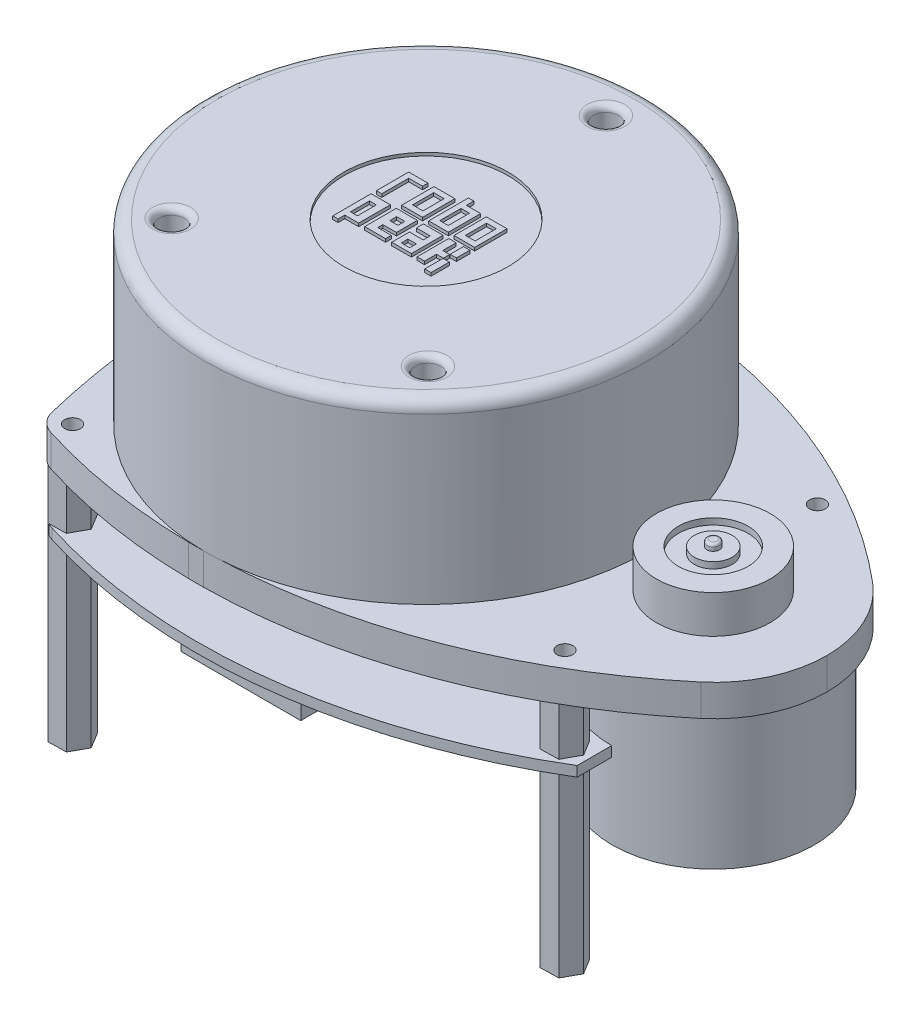
SolidWorks part; units mm, degrees
ref_plane "Спереди" through (0, 0, 0) normal (0, 0, 1) x (1, 0, 0)
ref_plane "Сверху" through (0, 0, 0) normal (0, 1, 0) x (1, 0, 0)
ref_plane "Справа" through (0, 0, 0) normal (1, 0, 0) x (0, 0, -1)
sketch "Эскиз1" plane through (0, 0, 0) normal (0, 1, 0) x (1, 0, 0)
  line L1 (-49.25, 35) -> (49.25, 35)
  line L2 (-49.25, 35) -> (-49.25, -35)
  line L3 (-49.25, -35) -> (49.25, -35)
  line L4 (49.25, 35) -> (49.25, -35)
  line L5 (-49.25, 35) -> (49.25, -35) construction
  line L6 (-49.25, -35) -> (49.25, 35) construction
  point P0 (0, 0)
  dimension "D1" = 98.5
  dimension "D2" = 70
extrude "Бобышка-Вытянуть1" add sketch "Эскиз1" along normal blind 5
sketch "Эскиз2" plane through (0, 5, 0) normal (0, 1, 0) x (1, 0, 0)
  line L0 (-49.25, 35) -> (-49.25, -35) construction
  circle A0 centre (-14.25, 0) radius 35
  point P2 (-49.25, 0)
  point P3 (-49.25, 0)
extrude "Бобышка-Вытянуть2" add sketch "Эскиз2" along normal blind 28.1
sketch "Эскиз3" plane through (0, 33.1, 0) normal (0, 1, 0) x (1, 0, 0)
  line L0 (-14.25, 0) -> (-14.25, 50000) construction
  line L1 (-14.25, -20) -> (-26.2883, -20) construction
  line L2 (-49.25, -35) -> (-14.25, -35) construction
  circle A0 centre (-14.25, 28.5) radius 2
  circle A1 centre (-34.5539, -20) radius 2
  circle A2 centre (6.0539, -20) radius 2
  arc A3 (-49.25, 0) -> (-14.25, -35) centre (-14.25, 0) ccw construction
  circle A4 centre (-14.25, 0) radius 35 construction
  dimension "D2" = 4
  dimension "D1" = 6.5
  dimension "D3" = 15
  dimension "D4" = 28.5
  dimension "D5" = 28.5
extrude "Вырез-Вытянуть1" cut sketch "Эскиз3" against normal blind 5
fillet "Скругление1" radius 2 1 edges at (-14.25, 33.1, 35)
fillet "Скругление2" radius 1 3 edges at (6.0539, 33.1, 22) (-34.5539, 33.1, 22) (-14.25, 33.1, -26.5)
sketch "Эскиз4" plane through (0, 33.1, 0) normal (0, 1, 0) x (1, 0, 0)
  line L0 (-22.1152, -6.9149) -> (-22.1152, -0.8316)
  line L1 (-22.1152, -0.8316) -> (-19.0735, -0.8316)
  line L2 (-19.0735, -0.8316) -> (-19.0735, -5.8538)
  line L3 (-19.0735, -5.8538) -> (-21.2663, -5.8538)
  line L4 (-21.2663, -5.8538) -> (-21.2663, -6.9149)
  line L5 (-21.2663, -6.9149) -> (-22.1152, -6.9149)
  line L6 (-22.1152, 0) -> (-22.1152, 5.1201)
  line L7 (-22.1152, 5.1201) -> (-19.0735, 5.1201)
  line L8 (-19.0735, 5.1201) -> (-19.0735, 4.2707)
  line L9 (-19.0735, 4.2707) -> (-21.2663, 4.2707)
  line L10 (-21.2663, 4.2707) -> (-21.2663, 0)
  line L11 (-21.2663, 0) -> (-22.1152, 0)
  line L12 (-21.2663, -1.9579) -> (-20.1699, -1.9579)
  line L13 (-20.1699, -1.9579) -> (-20.1699, -4.9509)
  line L14 (-20.1699, -4.9509) -> (-21.2663, -4.9509)
  line L15 (-21.2663, -4.9509) -> (-21.2663, -1.9579)
  line L16 (-13.8296, 0) -> (-13.8296, 6.293)
  line L17 (-18.1168, 0) -> (-14.8003, 0)
  line L18 (-18.1168, 0) -> (-18.1168, 5.1201)
  line L19 (-18.1168, 5.1201) -> (-14.8003, 5.1201)
  line L20 (-14.8003, 0) -> (-14.8003, 5.1201)
  line L21 (-9.8255, 5.1201) -> (-6.5494, 5.1201)
  line L22 (-9.8255, 5.1201) -> (-9.8255, 0)
  line L23 (-9.8255, 0) -> (-6.5494, 0)
  line L24 (-6.5494, 5.1201) -> (-6.5494, 0)
  line L25 (-8.9357, 4.2707) -> (-7.3988, 4.2707)
  line L26 (-8.9357, 4.2707) -> (-8.9357, 0.9137)
  line L27 (-8.9357, 0.9137) -> (-7.3988, 0.9137)
  line L28 (-7.3988, 4.2707) -> (-7.3988, 0.9137)
  line L29 (-17.3079, 4.2707) -> (-15.6497, 4.2707)
  line L30 (-17.3079, 4.2707) -> (-17.3079, 0.9137)
  line L31 (-17.3079, 0.9137) -> (-15.6497, 0.9137)
  line L32 (-15.6497, 4.2707) -> (-15.6497, 0.9137)
  line L33 (-12.9802, 4.2707) -> (-11.6455, 4.2707)
  line L34 (-12.9802, 4.2707) -> (-12.9802, 0.9137)
  line L35 (-12.9802, 0.9137) -> (-11.6455, 0.9137)
  line L36 (-11.6455, 4.2707) -> (-11.6455, 0.9137)
  line L37 (-12.9802, -4.142) -> (-11.6455, -4.142)
  line L38 (-12.9802, -4.142) -> (-12.9802, -5.1936)
  line L39 (-12.9802, -5.1936) -> (-11.6455, -5.1936)
  line L40 (-11.6455, -4.142) -> (-11.6455, -5.1936)
  line L41 (-16.9439, -1.9579) -> (-15.6497, -1.9579)
  line L42 (-16.9439, -1.9579) -> (-16.9439, -3.0499)
  line L43 (-16.9439, -3.0499) -> (-15.6497, -3.0499)
  line L44 (-15.6497, -1.9579) -> (-15.6497, -3.0499)
  line L46 (-7.5508, -0.7643) -> (-6.5494, -0.7643)
  line L47 (-7.5508, -0.7643) -> (-7.5508, -2.8858)
  line L48 (-7.5508, -2.8858) -> (-6.5494, -2.8858)
  line L49 (-6.5494, -0.7643) -> (-6.5494, -2.8858)
  line L50 (-6.5494, -6.9149) -> (-7.5508, -6.9149)
  line L51 (-6.5494, -6.9149) -> (-6.5494, -4.0216)
  line L52 (-6.5494, -4.0216) -> (-7.5508, -4.0216)
  line L53 (-13.8296, 6.293) -> (-12.9802, 6.293)
  line L54 (-12.9802, 6.293) -> (-12.9802, 5.1201)
  line L55 (-12.9802, 5.1201) -> (-10.7153, 5.1201)
  line L56 (-10.7153, 5.1201) -> (-10.7153, 0)
  line L57 (-10.7153, 0) -> (-13.8296, 0)
  line L58 (-9.8255, -0.8316) -> (-8.6437, -0.8316)
  line L59 (-8.6437, -0.8316) -> (-8.6437, -2.9608)
  line L60 (-8.6437, -2.9608) -> (-7.5508, -2.9608)
  line L61 (-9.8255, -0.8316) -> (-9.8255, -5.8538)
  line L62 (-9.8255, -5.8538) -> (-8.6437, -5.8538)
  line L63 (-8.6437, -5.8538) -> (-8.6437, -3.9573)
  line L64 (-8.6437, -3.9573) -> (-7.5508, -3.9573)
  line L65 (-7.5508, -2.9608) -> (-7.5508, -3.9573)
  line L66 (-13.8296, -0.8316) -> (-10.7153, -0.8316)
  line L67 (-10.7153, -0.8316) -> (-10.7153, -5.8538)
  line L68 (-10.7153, -5.8538) -> (-13.8296, -5.8538)
  line L69 (-13.8296, -5.8538) -> (-13.8296, -3.0499)
  line L70 (-13.8296, -3.0499) -> (-11.6455, -3.0499)
  line L71 (-11.6455, -3.0499) -> (-11.6455, -1.9408)
  line L72 (-11.6455, -1.9408) -> (-13.8296, -1.9408)
  line L73 (-13.8296, -1.9408) -> (-13.8296, -0.8316)
  line L74 (-18.1168, -0.8316) -> (-14.8003, -0.8316)
  line L75 (-14.8003, -0.8316) -> (-14.8003, -4.142)
  line L76 (-14.8003, -4.142) -> (-16.9439, -4.142)
  line L77 (-16.9439, -4.142) -> (-16.9439, -4.9509)
  line L78 (-16.9439, -4.9509) -> (-14.8003, -4.9509)
  line L79 (-14.8003, -4.9509) -> (-14.8003, -5.8538)
  line L80 (-14.8003, -5.8538) -> (-18.1168, -5.8538)
  line L81 (-18.1168, -5.8538) -> (-18.1168, -0.8316)
  line L82 (-7.5508, -6.9149) -> (-7.5508, -4.0216)
  circle A0 centre (-14.25, 0) radius 13
  dimension "D1" = 26
extrude "Вырез-Вытянуть3" cut sketch "Эскиз4" against normal blind 0.5 contours A0 L50 L82 L52 L51 L72 L73 L66 L67 L68 L69 L70 L71 L56 L57 L16 L53 L54 L55 L10 L11 L6 L7 L8 L9 L4 L5 L0 L1 L2 L3 L20 L17 L18 L19 L21 L24 L23 L22 L46 L49 L48 L47 | L32 L29 L30 L31 | L36 L33 L34 L35 | L28 L25 L26 L27 | L44 L41 L42 L43 | L15 L14 L13 L12 | L37 L40 L39 L38 region at (-20.7181, 33.1, 3.4544) region at (-8.1672, 33.1, -2.5922) region at (-16.4788, 33.1, -2.5922) region at (-12.3129, 33.1, -2.5922) region at (-16.2968, 33.1, 2.5039) region at (-14.2871, 33.1, -0.0991)
sketch "Эскиз5" plane through (0, 5, 0) normal (0, 1, 0) x (1, 0, 0)
  line L0 (-42.25, 30.7255) -> (-42.25, -39.5827) construction
  line L1 (27.75, 26.9972) -> (27.75, -49973.0028) construction
  line L2 (-49.25, 0) -> (49950.75, 0) construction
  circle A0 centre (-14.25, 0) radius 33 construction
  circle A1 centre (-42.25, 28) radius 1.25
  circle A2 centre (27.75, 20) radius 1.25
  circle A3 centre (27.75, -20) radius 1.25
  circle A4 centre (-42.25, -28) radius 1.25
  point P4 (-14.25, 33)
  dimension "D1" = 28
  dimension "D3" = 2.5
  dimension "D2" = 42
  dimension "D4" = 28
  dimension "D5" = 20
extrude "Вырез-Вытянуть4" cut sketch "Эскиз5" against normal blind 5
sketch "Эскиз6" plane through (0, 5, 0) normal (0, 1, 0) x (1, 0, 0)
  line L0 (49.25, 0) -> (50049.25, 0) construction
  line L1 (49.25, -35) -> (49.25, 35) construction
  circle A0 centre (31.25, 0) radius 9
  arc A1 (-14.25, -35) -> (-14.25, 35) centre (-14.25, 0) ccw construction
  point P4 (49.25, 0)
  dimension "D1" = 18
  dimension "D2" = 45.5
extrude "Бобышка-Вытянуть3" add sketch "Эскиз6" along normal blind 7
sketch "Эскиз7" plane through (0, 12, 0) normal (0, 1, 0) x (1, 0, 0)
  circle A0 centre (31.25, 0) radius 9
  circle A1 centre (31.25, 0) radius 0.9935
extrude "Вырез-Вытянуть5" cut sketch "Эскиз7" against normal blind 1
sketch "Эскиз8" plane through (0, 11, 0) normal (0, 1, 0) x (1, 0, 0)
  circle A0 centre (31.25, 0) radius 3.0011
  circle A1 centre (31.25, 0) radius 5.5217
extrude "Вырез-Вытянуть6" cut sketch "Эскиз8" against normal blind 1
fillet "Скругление3" radius 0.4 1 edges at (31.25, 12, 0.9935)
sketch "Эскиз9" plane through (0, 5, 0) normal (0, 1, 0) x (1, 0, 0)
  circle A0 centre (31.25, 0) radius 16
  dimension "D1" = 32
extrude "Бобышка-Вытянуть4" add sketch "Эскиз9" against normal blind 27
sketch "Эскиз10" plane through (0, 0, 0) normal (0, -1, 0) x (1, 0, 0)
  line L0 (-49.25, 0) -> (49950.75, 0) construction
  line L1 (-40.8546, 25.4729) -> (-39.3638, 27.9449)
  line L2 (-39.3638, 27.9449) -> (-40.7592, 30.472)
  line L3 (-40.7592, 30.472) -> (-43.6454, 30.5271)
  line L4 (-43.6454, 30.5271) -> (-45.1362, 28.0551)
  line L5 (-45.1362, 28.0551) -> (-43.7408, 25.528)
  line L6 (-43.7408, 25.528) -> (-40.8546, 25.4729)
  line L7 (29.2571, 22.4621) -> (26.3713, 22.5363)
  line L8 (26.3713, 22.5363) -> (24.8642, 20.0742)
  line L9 (24.8642, 20.0742) -> (26.2429, 17.5379)
  line L10 (26.2429, 17.5379) -> (29.1287, 17.4637)
  line L11 (29.1287, 17.4637) -> (30.6358, 19.9258)
  line L12 (30.6358, 19.9258) -> (29.2571, 22.4621)
  line L13 (30.6358, -19.9258) -> (29.2571, -22.4621)
  line L14 (29.1287, -17.4637) -> (30.6358, -19.9258)
  line L15 (26.2429, -17.5379) -> (29.1287, -17.4637)
  line L16 (24.8642, -20.0742) -> (26.2429, -17.5379)
  line L17 (26.3713, -22.5363) -> (24.8642, -20.0742)
  line L18 (29.2571, -22.4621) -> (26.3713, -22.5363)
  line L19 (-43.7408, -25.528) -> (-40.8546, -25.4729)
  line L20 (-45.1362, -28.0551) -> (-43.7408, -25.528)
  line L21 (-43.6454, -30.5271) -> (-45.1362, -28.0551)
  line L22 (-40.7592, -30.472) -> (-43.6454, -30.5271)
  line L23 (-39.3638, -27.9449) -> (-40.7592, -30.472)
  line L24 (-40.8546, -25.4729) -> (-39.3638, -27.9449)
  circle A0 centre (-42.25, 28) radius 2.5 construction
  circle A1 centre (27.75, 20) radius 2.5 construction
  circle A2 centre (27.75, -20) radius 2.5 construction
  circle A3 centre (-42.25, -28) radius 2.5 construction
  point P17 (27.75, 20)
  dimension "D1" = 5
  dimension "D2" = 5
extrude "Бобышка-Вытянуть5" add sketch "Эскиз10" along normal blind 38
sketch "Эскиз11" plane through (0, 5, 0) normal (0, 1, 0) x (1, 0, 0)
  circle A0 centre (-14.25, 0) radius 26
  dimension "D1" = 52
extrude "Бобышка-Вытянуть6" add sketch "Эскиз11" against normal blind 8
fillet "Скругление4" radius 1 1 edges at (-14.25, -3, 26)
sketch "Эскиз12" plane through (0, 5, 0) normal (0, 1, 0) x (1, 0, 0)
  line L1 (49.25, -35) -> (49.25, 35) construction
  line L2 (-49.25, 0) -> (-50049.25, 0) construction
  line L4 (-54.0511, 37.7308) -> (52.2004, 37.7308)
  line L5 (-54.0511, 37.7308) -> (-54.0511, -37.8351)
  line L6 (-54.0511, -37.8351) -> (52.2004, -37.8351)
  line L7 (52.2004, 37.7308) -> (52.2004, -37.8351)
  arc A0 (-49.25, 0) -> (-45.5286, 27.9743) centre (86.6751, -3.8473) cw
  circle A1 centre (-14.25, 0) radius 35 construction
  arc A3 (49.25, 0) -> (42.909, 13.5993) centre (31.4018, -0.0442) ccw
  arc A4 (-49.25, 0) -> (-14.25, -35) centre (-14.25, 0) ccw construction
  arc A5 (-42.835, 30.8555) -> (42.909, 13.5993) centre (-15.6796, -55.8665) cw
  arc A6 (-45.5286, 27.9743) -> (-42.835, 30.8555) centre (-41.6397, 27.0383) cw
  arc A7 (-45.5286, -27.9743) -> (-42.835, -30.8555) centre (-41.6397, -27.0383) ccw
  arc A8 (-42.835, -30.8555) -> (42.909, -13.5993) centre (-15.6796, 55.8665) ccw
  arc A9 (49.25, 0) -> (42.909, -13.5993) centre (31.4018, 0.0442) cw
  arc A10 (-49.25, 0) -> (-45.5286, -27.9743) centre (86.6751, 3.8473) ccw
  dimension "D1" = 4
extrude "Вырез-Вытянуть7" cut sketch "Эскиз12" against normal blind 8
fillet "Скругление5" radius 100 1 edges at (-49.25, 2.5, 0)
sketch "Эскиз13" plane through (0, 0, 0) normal (0, -1, 0) x (1, 0, 0)
  line L0 (31.5536, 21.8603) -> (31.5536, 16.4)
  line L1 (31.5536, -16.4) -> (31.5536, -21.8603)
  arc A0 (-49.0982, 0) -> (-45.3768, 27.9743) centre (86.8269, -3.8473) cw
  arc A1 (31.5536, 16.4) -> (31.5536, -16.4) centre (31.5536, 0) ccw
  arc A2 (-42.6831, 30.8555) -> (31.5536, 21.8603) centre (-15.5278, -55.8665) cw
  arc A3 (-45.3768, 27.9743) -> (-42.6831, 30.8555) centre (-41.4878, 27.0383) cw
  arc A4 (-45.3768, -27.9743) -> (-42.6831, -30.8555) centre (-41.4878, -27.0383) ccw
  arc A5 (-42.6831, -30.8555) -> (31.5536, -21.8603) centre (-15.5278, 55.8665) ccw
  arc A7 (-49.0982, 0) -> (-45.3768, -27.9743) centre (86.8269, 3.8473) ccw
  arc A8 (-48.5248, 10.6929) -> (-48.5248, -10.6929) centre (50.9018, 0) ccw construction
  point P16 (-49.0982, 0)
  point P21 (-49.0982, 0)
  dimension "D1" = 4
  dimension "D2" = 32.8
extrude "Бобышка-Вытянуть7" add sketch "Эскиз13" along normal blind 1.6 from offset 8
sketch "Эскиз14" plane through (0, -9.6, 0) normal (0, -1, 0) x (1, 0, 0)
  line L1 (-24.0982, 30) -> (-4.0982, 30)
  line L2 (-24.0982, 30) -> (-24.0982, 25)
  line L3 (-24.0982, 25) -> (-4.0982, 25)
  line L4 (-4.0982, 30) -> (-4.0982, 25)
  circle A0 centre (-14.25, 0) radius 35 construction
  point P4 (-14.0982, 30)
  dimension "D1" = 5
  dimension "D2" = 20
  dimension "D3" = 35
  dimension "D4" = 30
extrude "Бобышка-Вытянуть8" add sketch "Эскиз14" along normal blind 6
chamfer "Фаска1" distance 1 angle 45 1 edges at (-24.0982, -12.6, 30)
